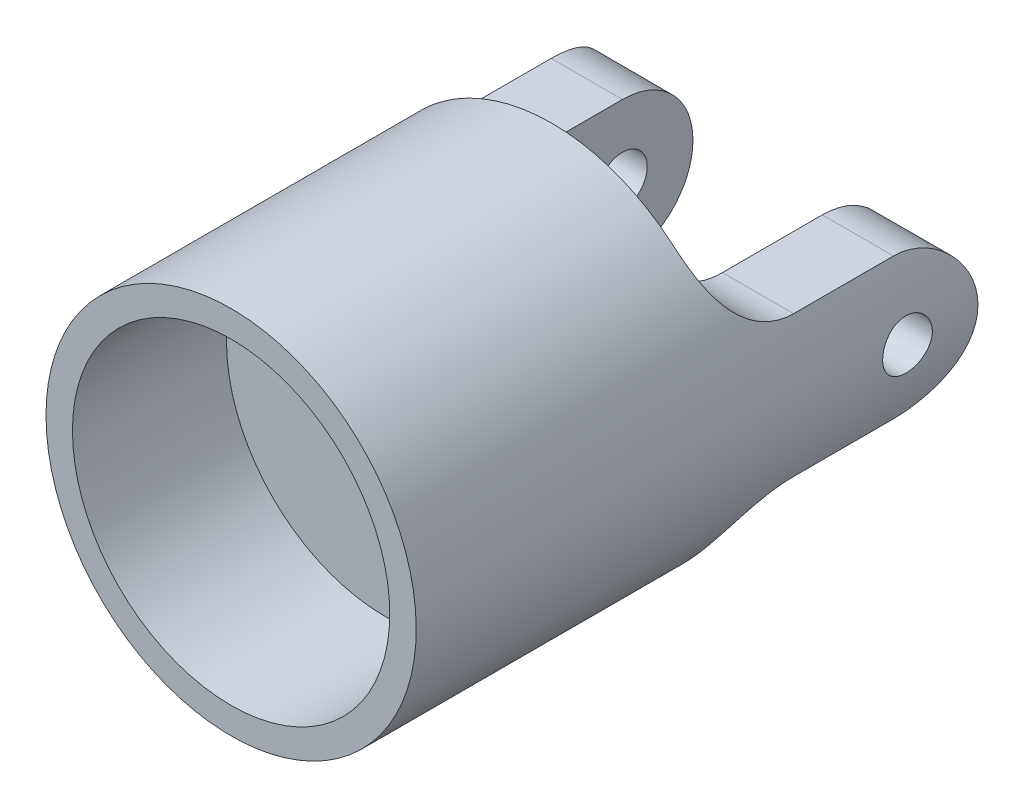
SolidWorks part; units mm, degrees
material "AISI 1020"
ref_plane "Front Plane" through (0, 0, 0) normal (0, 0, 1) x (1, 0, 0)
ref_plane "Top Plane" through (0, 0, 0) normal (0, 1, 0) x (1, 0, 0)
ref_plane "Right Plane" through (0, 0, 0) normal (1, 0, 0) x (0, 0, -1)
sketch "Sketch1" plane through (0, 0, 0) normal (1, 0, 0) x (0, 0, -1)
  line L0 (0, 0) -> (-34.925, 0) construction
  line L1 (-34.925, 11.1125) -> (-34.925, 9.525)
  line L2 (-34.925, 9.525) -> (-15.925, 9.525)
  line L3 (-15.925, 9.525) -> (-15.925, 0)
  line L4 (-15.925, 0) -> (11.1125, 0)
  line L5 (-34.925, 11.1125) -> (11.1125, 11.1125)
  line L6 (11.1125, 11.1125) -> (11.1125, 0)
  arc A0 (0, 11.1125) -> (11.1125, 0) centre (0, 0) cw construction
  dimension "D3" = 19.05
  dimension "D1" = 34.925
  dimension "D2" = 19
  dimension "D4" = 22.225
revolve "Revolve1" add sketch "Sketch1" angle 360 about L0
sketch "Sketch3" plane through (0, 0, 0) normal (1, 0, 0) x (0, 0, -1)
  line L0 (11.1125, 11.1125) -> (-34.925, 11.1125) construction
  line L1 (11.1125, 11.1125) -> (-10.2333, 11.1125)
  line L2 (-34.925, -11.1125) -> (11.1125, -11.1125) construction
  line L3 (-10.2333, -11.1125) -> (11.1125, -11.1125)
  line L4 (11.1125, -11.1125) -> (11.1125, 11.1125) construction
  line L5 (11.1125, -11.1125) -> (11.1125, 11.1125)
  line L6 (-10.2333, 8.4667) -> (-10.2333, 11.1125)
  line L7 (-10.2333, -8.4667) -> (-10.2333, -11.1125)
  line L8 (0, 4.2333) -> (-6, 4.2333)
  line L9 (0, -4.2333) -> (-6, -4.2333)
  arc A0 (0, -4.2333) -> (0, 4.2333) centre (0, 0) ccw
  arc A1 (-10.2333, 8.4667) -> (-6, 4.2333) centre (-6, 8.4667) ccw
  arc A2 (-10.2333, -8.4667) -> (-6, -4.2333) centre (-6, -8.4667) cw
  dimension "D1" = 4.2333
  dimension "D2" = 4.2333
  dimension "D3" = 6
extrude "Cut-Extrude1" cut sketch "Sketch3" against normal through all and the other way through all
sketch "Sketch4" plane through (0, 0, 0) normal (0, 1, 0) x (1, 0, 0)
  line L0 (-7.1974, -10.2333) -> (7.1974, -10.2333) construction
  line L1 (-2.825, -10.2333) -> (2.825, -10.2333)
  line L2 (0, 0) -> (0, -10.2333) construction
  line L4 (-6, -7.0583) -> (-6, 4.2333)
  line L5 (11.1125, 4.2333) -> (-11.1125, 4.2333) construction
  line L6 (6, 4.2333) -> (6, -7.0583)
  line L7 (6, 4.2333) -> (-6, 4.2333)
  arc A0 (-6, -7.0583) -> (-2.825, -10.2333) centre (-2.825, -7.0583) ccw
  arc A1 (6, -7.0583) -> (2.825, -10.2333) centre (2.825, -7.0583) cw
  point P14 (-6, -10.2333)
  point P17 (6, -10.2333)
  dimension "D2" = 3.175
  dimension "D1" = 12
extrude "Cut-Extrude2" cut sketch "Sketch4" against normal through all and the other way through all
sketch3d "3DSketch1"
  line L0 (0, 0, 0) -> (0, 0, 34.925)
  line L1 (0, 0, 34.925) -> (0, 0, 10.2333) construction
  line L2 (0, 0, 34.925) -> (0, 0, 15.925) construction
ref_axis "Axis1" through (39.0367, 0, 0) along (-1, 0, 0)
sketch "Sketch5" plane through (-6, 0, 0) normal (1, 0, 0) x (0, 0, -1)
  circle A0 centre (0, 0) radius 1.49
extrude "Cut-Extrude3" cut sketch "Sketch5" against normal blind 10 and the other way blind 20
sketch "Sketch6" plane through (0, 0, 15.925) normal (0, 0, 1) x (1, 0, 0)
  circle A2 centre (0, 0) radius 9.525
  circle A3 centre (0, 0) radius 9.525
  dimension "D1" = 0
extrude "Boss-Extrude1" add sketch "Sketch6" along normal blind 4.32
sketch "Sketch7" plane through (0, 0, 34.925) normal (0, 0, 1) x (1, 0, 0)
  line L1 (-13.6071, -14.2229) -> (16.624, -14.2229)
  line L2 (-13.6071, -14.2229) -> (-13.6071, 12.6757)
  line L3 (-13.6071, 12.6757) -> (16.624, 12.6757)
  line L4 (16.624, -14.2229) -> (16.624, 12.6757)
extrude "Cut-Extrude4" cut sketch "Sketch7" against normal blind 5.43
